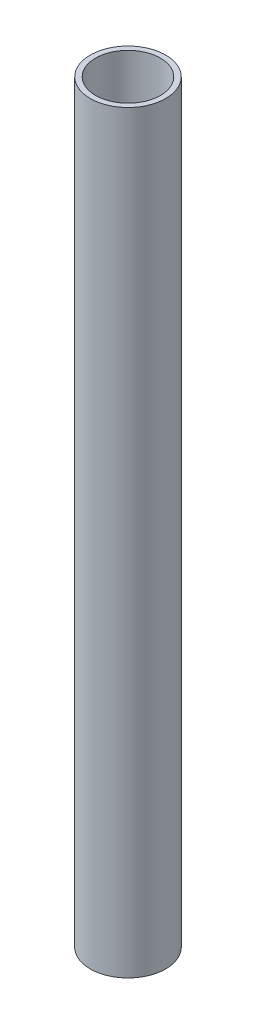
SolidWorks part; units mm, degrees
material "Простая углеродистая сталь"
ref_plane "Спереди" through (0, 0, 0) normal (0, 0, 1) x (1, 0, 0)
ref_plane "Сверху" through (0, 0, 0) normal (0, 1, 0) x (1, 0, 0)
ref_plane "Справа" through (0, 0, 0) normal (1, 0, 0) x (0, 0, -1)
sketch "Эскиз1" plane through (0, 0, 0) normal (0, 1, 0) x (1, 0, 0)
  circle A0 centre (0, 0) radius 25
extrude "Вытянуть-Тонкостенный1" add sketch "Эскиз1" along normal blind 500 thin thin type one direction reverse wall 3.5
